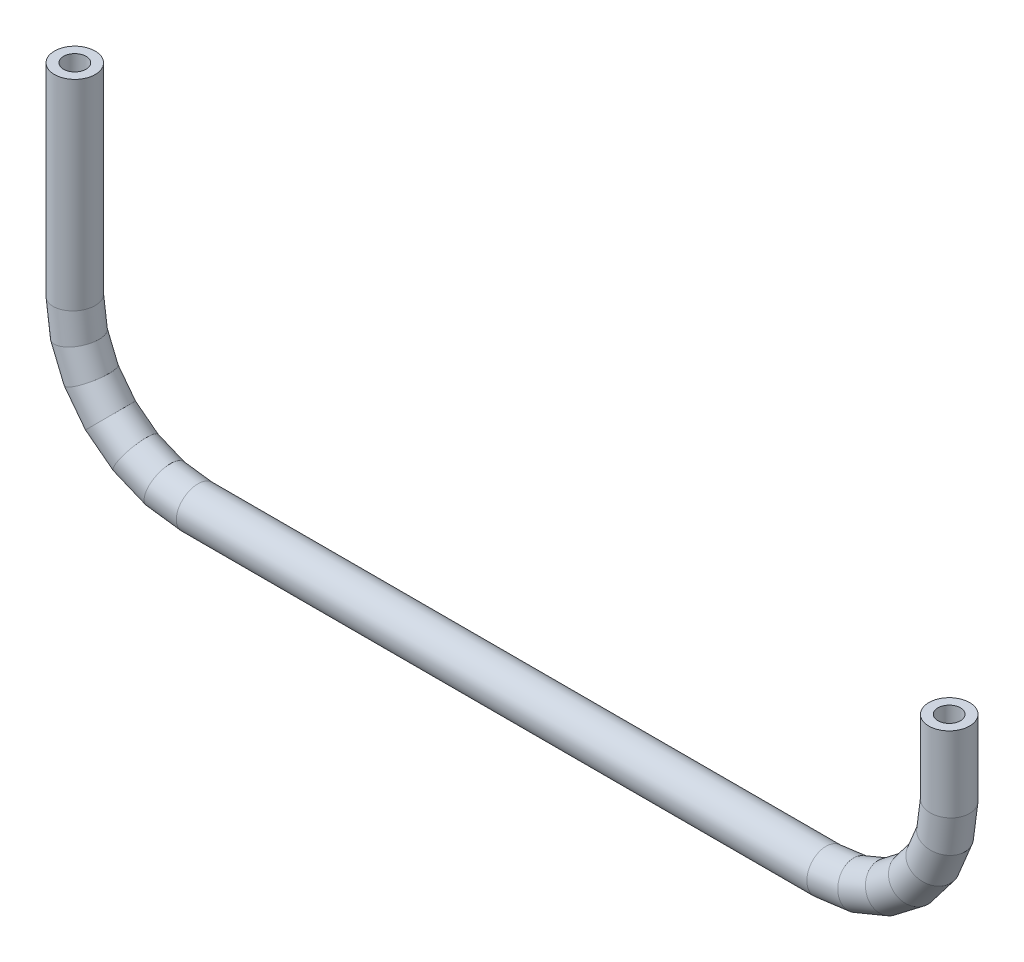
SolidWorks part; units mm, degrees
ref_plane "Front Plane" through (0, 0, 0) normal (0, 0, 1) x (1, 0, 0)
ref_plane "Top Plane" through (0, 0, 0) normal (0, 1, 0) x (1, 0, 0)
ref_plane "Right Plane" through (0, 0, 0) normal (1, 0, 0) x (0, 0, -1)
sketch3d "Path"
  line L0 (-118.15, -19.9, 0) -> (-118.15, -35.6, 0)
  line L1 (-118.15, -35.6, 0) -> (-117.8263, -38.0588, 0)
  line L2 (-117.8263, -38.0588, 0) -> (-116.8772, -40.35, 0)
  line L3 (-116.8772, -40.35, 0) -> (-115.3675, -42.3175, 0)
  line L4 (-115.3675, -42.3175, 0) -> (-113.4, -43.8272, 0)
  line L5 (-113.4, -43.8272, 0) -> (-111.1088, -44.7763, 0)
  line L6 (-111.1088, -44.7763, 0) -> (-108.65, -45.1, 0)
  line L7 (-108.65, -45.1, 0) -> (-59.5, -45.1, 0)
  line L8 (-59.5, -45.1, 0) -> (-57.0412, -44.7763, 0)
  line L9 (-57.0412, -44.7763, 0) -> (-54.75, -43.8272, 0)
  line L10 (-54.75, -43.8272, 0) -> (-52.7825, -42.3175, 0)
  line L11 (-52.7825, -42.3175, 0) -> (-51.2728, -40.35, 0)
  line L12 (-51.2728, -40.35, 0) -> (-50.3237, -38.0588, 0)
  line L13 (-50.3237, -38.0588, 0) -> (-50, -35.6, 0)
  line L14 (-50, -35.6, 0) -> (-50, -29.8, 0)
ref_plane "Start Plane" through (0, -19.9, 0) normal (0, 1, 0) x (1, 0, 0)
sketch "Profile" plane through (0, -19.9, 0) normal (0, 1, 0) x (1, 0, 0)
  circle A0 centre (-118.15, 0) radius 1.5875
  circle A1 centre (-118.15, 0) radius 0.8775
sweep "Tube" add profiles "Profile" path "Path"
ref_axis "Engine Axis" through (-44.8462, 0, 0) along (-1, 0, 0)
